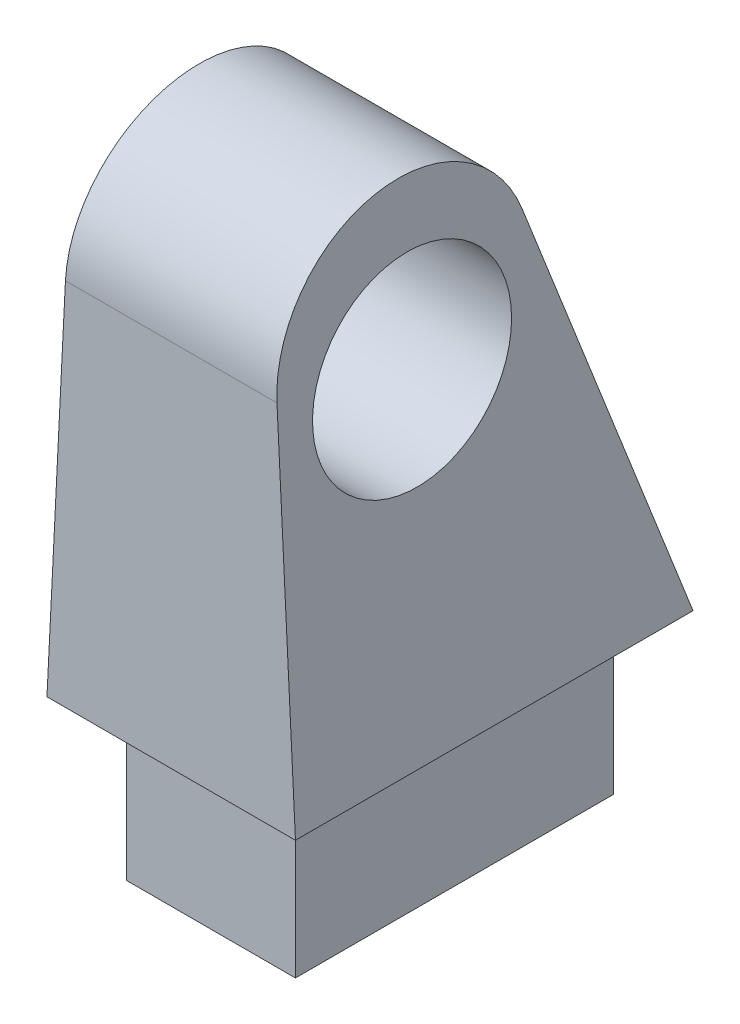
SolidWorks part; units mm, degrees
ref_plane "Front Plane" through (0, 0, 0) normal (0, 0, 1) x (1, 0, 0)
ref_plane "Top Plane" through (0, 0, 0) normal (0, 1, 0) x (1, 0, 0)
ref_plane "Right Plane" through (0, 0, 0) normal (1, 0, 0) x (0, 0, -1)
sketch "Sketch1" plane through (0, 0, 0) normal (1, 0, 0) x (0, 0, -1)
  line L0 (1.547, 13.1962) -> (6.35, 0)
  line L1 (6.35, 0) -> (-6.35, 0)
  line L2 (-6.35, 0) -> (-6.35, 11.8037)
  line L3 (-10.0809, 15.875) -> (13.4038, 15.875) construction
  arc A3 (1.547, 13.1962) -> (-6.35, 11.8037) centre (-2.2787, 11.8037) ccw
  circle A4 centre (-2.0941, 10.6275) radius 3.175
  point P8 (0, 0)
  dimension "D1" = 15.875
  dimension "D3" = 70
  dimension "D4" = 6.35
  dimension "D2" = 12.7
extrude "Boss-Extrude1" add sketch "Sketch1" along normal blind 7.9375
sketch "Sketch2" plane through (0, 0, 6.35) normal (0, 0, 1) x (1, 0, 0)
  line L0 (0, 0) -> (7.9375, 0)
  line L1 (7.9375, 0) -> (7.1437, 15.875)
  line L2 (7.9375, 15.875) -> (0, 15.875) construction
  line L3 (7.1437, 15.875) -> (0.7938, 15.875)
  line L4 (0.7938, 15.875) -> (0, 0)
  point P8 (3.9688, 15.875)
  point P9 (3.9688, 0)
  dimension "D1" = 6.35
extrude "Cut-Extrude1" cut sketch "Sketch2" against normal through all flip side to cut
sketch "Sketch3" plane through (0, 0, 0) normal (0, -1, 0) x (1, 0, 0)
  line L0 (7.9375, 6.35) -> (0, 6.35) construction
  line L1 (1.27, -5.08) -> (6.6675, -5.08)
  line L2 (1.27, -5.08) -> (1.27, 5.08)
  line L3 (1.27, 5.08) -> (6.6675, 5.08)
  line L4 (6.6675, -5.08) -> (6.6675, 5.08)
  line L5 (1.27, -5.08) -> (6.6675, 5.08) construction
  line L6 (1.27, 5.08) -> (6.6675, -5.08) construction
  line L7 (7.9375, 6.35) -> (7.9375, -6.35) construction
  point P0 (3.9688, 0)
  point P12 (3.9688, 6.35)
  dimension "D1" = 1.27
  dimension "D2" = 1.27
extrude "Boss-Extrude2" add sketch "Sketch3" along normal blind 5.08
sketch "Sketch4" plane through (0, 0, 0) normal (0, -1, 0) x (1, 0, 0)
  line L0 (0, 0) -> (7.9375, 0)
  line L1 (0, 6.35) -> (0, -6.35) construction
  line L2 (7.9375, 6.35) -> (7.9375, -6.35) construction
  point P6 (3.9688, 0)
ref_plane "Plane1" through (3.9688, 0, 0) normal (-1, 0, 0) x (0, 0, 1)
equation "\"D1@Boss-Extrude1\"=5/16in"
